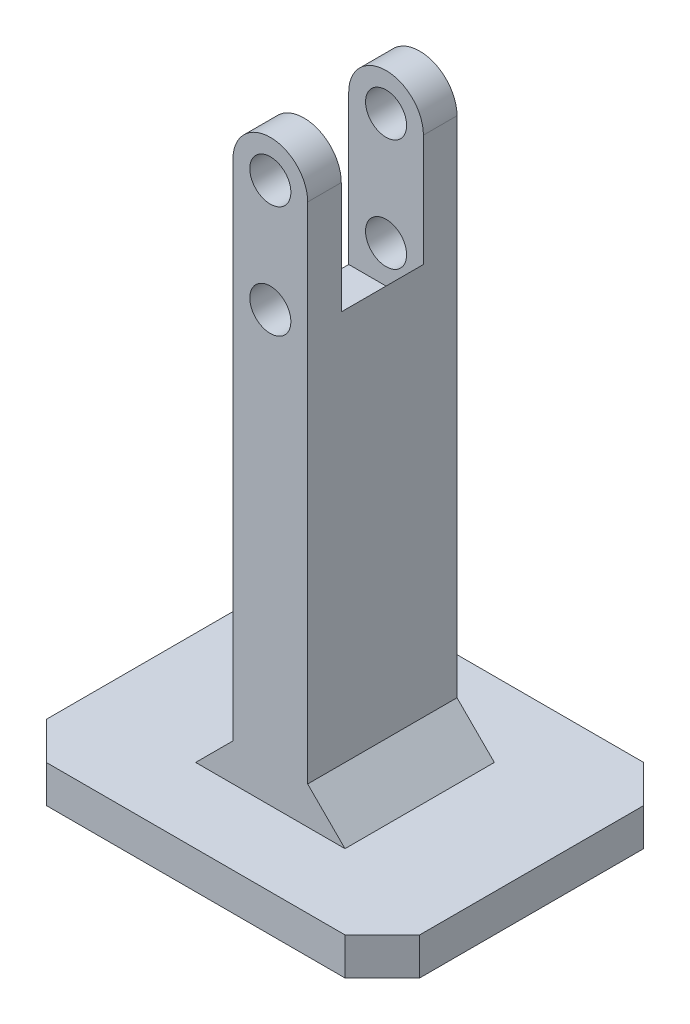
SolidWorks part; units mm, degrees
material "ABS"
ref_plane "Front Plane" through (0, 0, 0) normal (0, 0, 1) x (1, 0, 0)
ref_plane "Top Plane" through (0, 0, 0) normal (0, 1, 0) x (1, 0, 0)
ref_plane "Right Plane" through (0, 0, 0) normal (1, 0, 0) x (0, 0, -1)
ref_axis "X" through (-88.99, 0, 0) along (1, 0, 0)
ref_axis "Y" through (0, 55, 0) along (0, -1, 0)
ref_axis "Z" through (0, 0, -88.99) along (0, 0, 1)
sketch "Sketch1" plane through (0, 0, 0) normal (0, 0, 1) x (1, 0, 0)
  line L0 (0, 7.5) -> (0, -7.5) construction
  line L1 (0, -7.5) -> (0, -67.5) construction
  line L2 (5, -65) -> (5, 7.5)
  line L3 (-25, -65) -> (25, -65)
  line L4 (-25, -65) -> (-25, -70)
  line L5 (-25, -70) -> (25, -70)
  line L6 (25, -65) -> (25, -70)
  line L7 (-25, -65) -> (25, -70) construction
  line L8 (-25, -70) -> (25, -65) construction
  line L9 (-5, 7.5) -> (-5, -65)
  line L10 (0, -12.5) -> (-5, -12.5)
  arc A0 (5, 7.5) -> (-5, 7.5) centre (0, 7.5) ccw
  circle A1 centre (0, 7.5) radius 2.5 construction
  circle A2 centre (0, -7.5) radius 2.5 construction
  arc A3 (5, -7.5) -> (0, -12.5) centre (0, -7.5) cw
  point P4 (0, 0)
  dimension "D5" = 5
  dimension "D6" = 5
  dimension "D1" = 15
  dimension "D2" = 5
  dimension "D3" = 50
  dimension "D4" = 60
extrude "Boss-Extrude1" add sketch "Sketch1" along normal mid plane 20 contours L2 A0 L9 L3 | L6 L3 L4 L5 | A3 L2 A0 L9 L10 region at (0.0393, -38.4732, 0) region at (0, -67.5, 0) region at (-0.0891, -0.2611, 0)
sketch "Sketch4" plane through (0, 0, 10) normal (0, 0, 1) x (1, 0, 0)
  point P0 (0, 7.5)
  point P3 (0, -7.5)
hole_wizard "M5 Clearance Hole1" positions "Sketch4" profile "Sketch3" hole size "M5" standard "ANSI Metric" end condition through all
sketch "Sketch3" plane through (0, 7.5, 10) normal (1, 0, 0) x (0, -1, 0)
  line L0 (0, 0) -> (0, 20)
  line L1 (0, 20) -> (2.75, 20)
  line L2 (2.75, 20) -> (2.75, 0)
  line L5 (2.75, 0) -> (0, 0)
  line L11 (0, -6.35) -> (0, 107.95) construction
  dimension "Thru Hole Dia." = 5.5
  dimension "Thru Hole Depth" = 20
extrude "Cut-Extrude1" cut sketch "Sketch1<3>" against normal mid plane 11 contours A3 L2 A0 L9 L10 region at (-0.0891, -0.2611, 0)
sketch "Sketch1<3>" plane through (0, 0, 0) normal (0, 0, 1) x (1, 0, 0) same geometry as "Sketch1"
extrude "Boss-Extrude2" add sketch "Sketch1<4>" along normal mid plane 40 contours L6 L3 L4 L5 region at (0, -67.5, 0)
sketch "Sketch1<4>" plane through (0, 0, 0) normal (0, 0, 1) x (1, 0, 0) same geometry as "Sketch1"
chamfer "Chamfer1" distance 5 angle 45 6 edges at (5, -65, 0) (-5, -65, 0) (25, -67.5, -20) (-25, -67.5, -20) (25, -67.5, 20) (-25, -67.5, 20)
